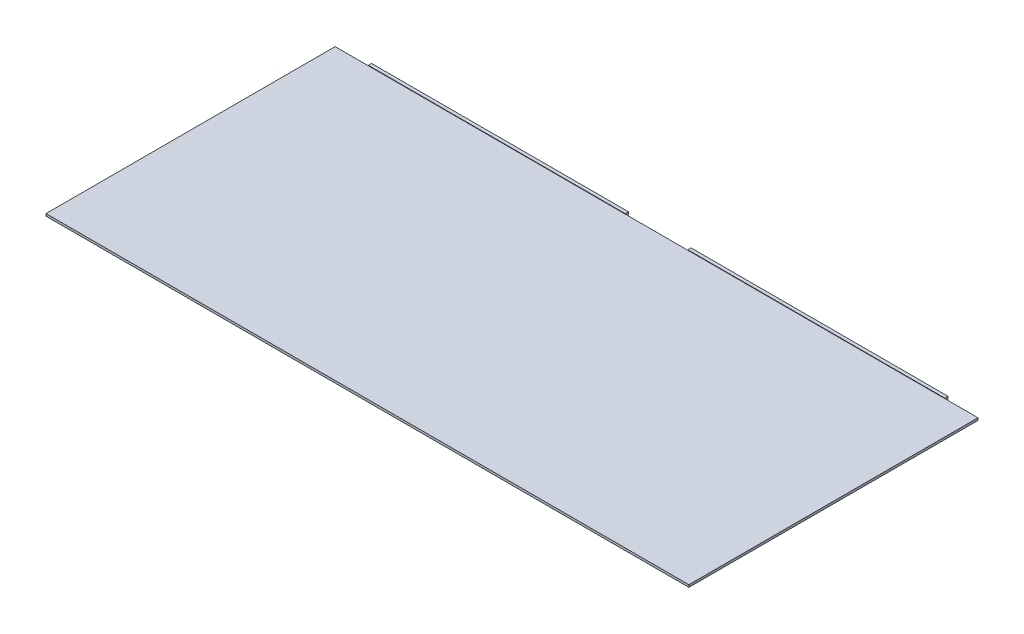
SolidWorks part; units mm, degrees
material "6061-T6 (SS)"
ref_plane "X-Y Datum" through (0, 0, 0) normal (0, 0, 1) x (1, 0, 0)
ref_plane "X-Z Datum" through (0, 0, 0) normal (0, 1, 0) x (1, 0, 0)
ref_plane "Y-Z Datum" through (0, 0, 0) normal (1, 0, 0) x (0, 0, -1)
sketch "Sketch1" plane through (0, 0, 0) normal (0, 1, 0) x (1, 0, 0)
  line L1 (-317.6778, 142.875) -> (317.6778, 142.875)
  line L2 (-317.6778, 142.875) -> (-317.6778, -142.875)
  line L3 (-317.6778, -142.875) -> (317.6778, -142.875)
  line L4 (317.6778, 142.875) -> (317.6778, -142.875)
  line L5 (-317.6778, 142.875) -> (317.6778, -142.875) construction
  line L6 (-317.6778, -142.875) -> (317.6778, 142.875) construction
  point P0 (0, 0)
  dimension "D1" = 635.3556
  dimension "D2" = 285.75
extrude "Boss-Extrude1" add sketch "Sketch1" along normal mid plane 2.286
sketch "Sketch2" plane through (0, 0, -142.875) normal (0, 0, -1) x (-1, 0, 0)
  line L20 (-317.6778, -1.143) -> (317.6778, -1.143) construction
  line L21 (-284.8229, -1.143) -> (-30.8229, -1.143)
  line L22 (30.8229, -1.143) -> (284.8229, -1.143)
  line L40 (30.8229, -1.143) -> (30.8229, 1.5875)
  line L41 (30.8229, 1.5875) -> (284.8229, 1.5875)
  line L42 (284.8229, 1.5875) -> (284.8229, -1.143)
  line L56 (-284.8229, -1.143) -> (-284.8229, 1.5875)
  line L57 (-284.8229, 1.5875) -> (-30.8229, 1.5875)
  line L58 (-30.8229, 1.5875) -> (-30.8229, -1.143)
extrude "Boss-Extrude2" add sketch "Sketch2" along normal blind 3.175
